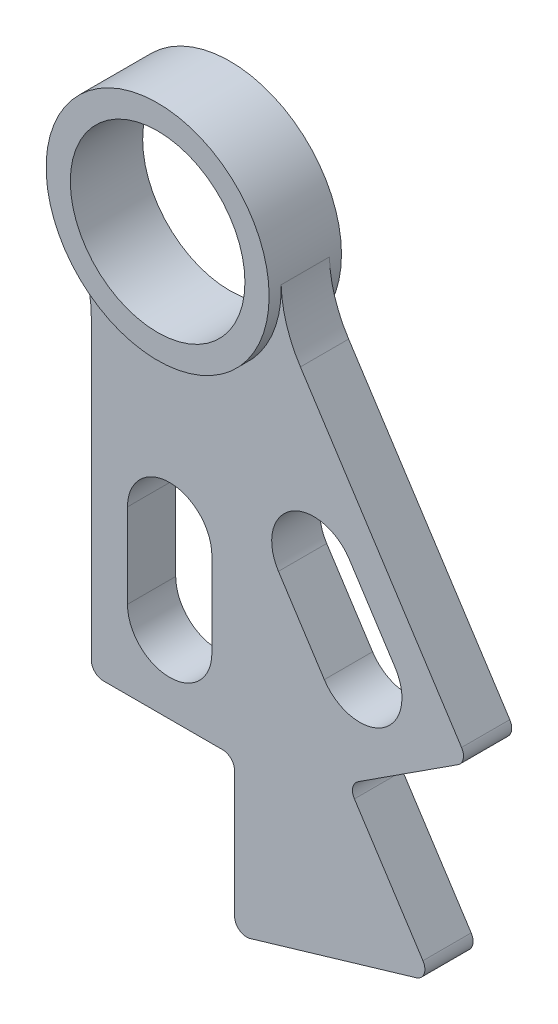
SolidWorks part; units mm, degrees
material "AISI 4130 Steel, annealed at 865C"
ref_plane "X-Y Datum" through (0, 0, 0) normal (0, 0, 1) x (1, 0, 0)
ref_plane "X-Z Datum" through (0, 0, 0) normal (0, 1, 0) x (1, 0, 0)
ref_plane "Y-Z Datum" through (0, 0, 0) normal (1, 0, 0) x (0, 0, -1)
sketch "Sketch1" plane through (0, 0, 0) normal (0, 0, 1) x (1, 0, 0)
  line L0 (0, -46.0556) -> (0, -34.9431) construction
  line L1 (-5.5563, -46.0556) -> (-5.5563, -34.9431)
  line L2 (5.5563, -46.0556) -> (5.5563, -34.9431)
  line L3 (25.0228, -38.6649) -> (18.9852, -29.3357) construction
  line L4 (20.3582, -41.6837) -> (14.3206, -32.3545)
  line L5 (29.6874, -35.6461) -> (23.6498, -26.3169)
  line L6 (-10.3187, -15.7343) -> (-10.3187, -56.3743)
  line L7 (-10.3187, -56.3743) -> (10.3188, -56.3743)
  line L10 (21.9663, -52.9341) -> (39.292, -41.7214)
  line L11 (39.292, -41.7214) -> (17.2116, -7.603)
  line L13 (8.5408, -76.6943) -> (34.4992, -69.0273)
  line L14 (0, -51.6118) -> (0, -56.3743) construction
  line L15 (28.0416, -43.3295) -> (30.6292, -47.3278) construction
  line L16 (26.6686, -30.9815) -> (30.6669, -28.3939) construction
  line L17 (-5.5563, -40.4993) -> (-10.3187, -40.4993) construction
  line L18 (-10.3187, -24.6243) -> (10.3187, -24.6243) construction
  line L19 (10.3187, -24.6243) -> (10.3188, -56.3743) construction
  line L20 (5.5563, -40.4993) -> (10.3188, -40.4993) construction
  line L21 (0, -29.3868) -> (0, -24.6243) construction
  line L22 (21.9663, -52.9341) -> (4.716, -26.2791) construction
  line L23 (4.716, -26.2791) -> (22.0417, -15.0664) construction
  line L24 (17.3394, -37.0191) -> (13.3411, -39.6066) construction
  line L25 (15.9664, -24.671) -> (13.3788, -20.6728) construction
  line L31 (8.5408, -56.3743) -> (8.5408, -76.6943)
  line L33 (23.459, -51.9681) -> (34.4992, -69.0273)
  line L34 (218.5438, -337.6911) -> (0, 0) construction
  line L35 (0, -404.7476) -> (0, 0) construction
  circle A0 centre (0, 0) radius 11.4954
  arc A1 (-5.5563, -46.0556) -> (5.5563, -46.0556) centre (0, -46.0556) ccw
  arc A2 (5.5563, -34.9431) -> (-5.5563, -34.9431) centre (0, -34.9431) ccw
  arc A3 (20.3582, -41.6837) -> (29.6874, -35.6461) centre (25.0228, -38.6649) ccw
  arc A4 (23.6498, -26.3169) -> (14.3206, -32.3545) centre (18.9852, -29.3357) ccw
  arc A5 (14.673, 0.4911) -> (-12.5852, -7.5598) centre (0, 0) ccw
  arc A6 (17.2116, -7.603) -> (14.673, 0.4911) centre (30.5391, 1.0221) cw
  arc A7 (-10.3187, -15.7343) -> (-12.5852, -7.5598) centre (-26.1937, -15.7343) ccw
  arc A14 (-12.5852, -7.5598) -> (14.673, 0.4911) centre (0, 0) ccw
  point P5 (0, -40.4993)
  point P11 (22.004, -34.0003)
  point P24 (30.6292, -47.3278)
  point P31 (0, -56.3743)
  point P37 (23.459, -51.9681)
  point P39 (28.0416, -43.3295)
  point P51 (8.5408, -56.3743)
  dimension "D1" = 22.9908
  dimension "D2" = 14.6812
  dimension "D8" = 15.875
  dimension "D9" = 1.778
  dimension "D3" = 1.778
  dimension "D4" = 4.7625
  dimension "D5" = 31.75
  dimension "D6" = 8.89
  dimension "D7" = 8.89
  dimension "D10" = 20.32
extrude "Boss-Extrude2" add sketch "Sketch1" along normal mid plane 9.525 contours A5 A14 A0 region at (-4.041, 13.6817, 0)
extrude "Boss-Extrude3" add sketch "Sketch1<4>" along normal mid plane 6.35 contours A14 A7 L6 L7 L10 L11 A6 A4 L5 A3 L4 A2 L2 A1 L1 region at (11.9519, -40.4658, 0)
sketch "Sketch1<4>" plane through (0, 0, 0) normal (0, 0, 1) x (1, 0, 0) same geometry as "Sketch1"
fillet "Fillet1" radius 1.5875 6 edges at (-10.3187, -56.3743, 0) (39.292, -41.7214, 0) (8.5408, -76.6943, 0) (34.4992, -69.0273, 0) (23.459, -51.9681, 0) (8.5408, -56.3743, 0)
sketch "Sketch2" plane through (0, 0, 4.7625) normal (0, 0, 1) x (1, 0, 0)
  point P0 (0, 0)
sketch "Sketch3" plane through (0, 0, -4.7625) normal (0, 0, -1) x (-1, 0, 0)
  point P0 (0, 0)
